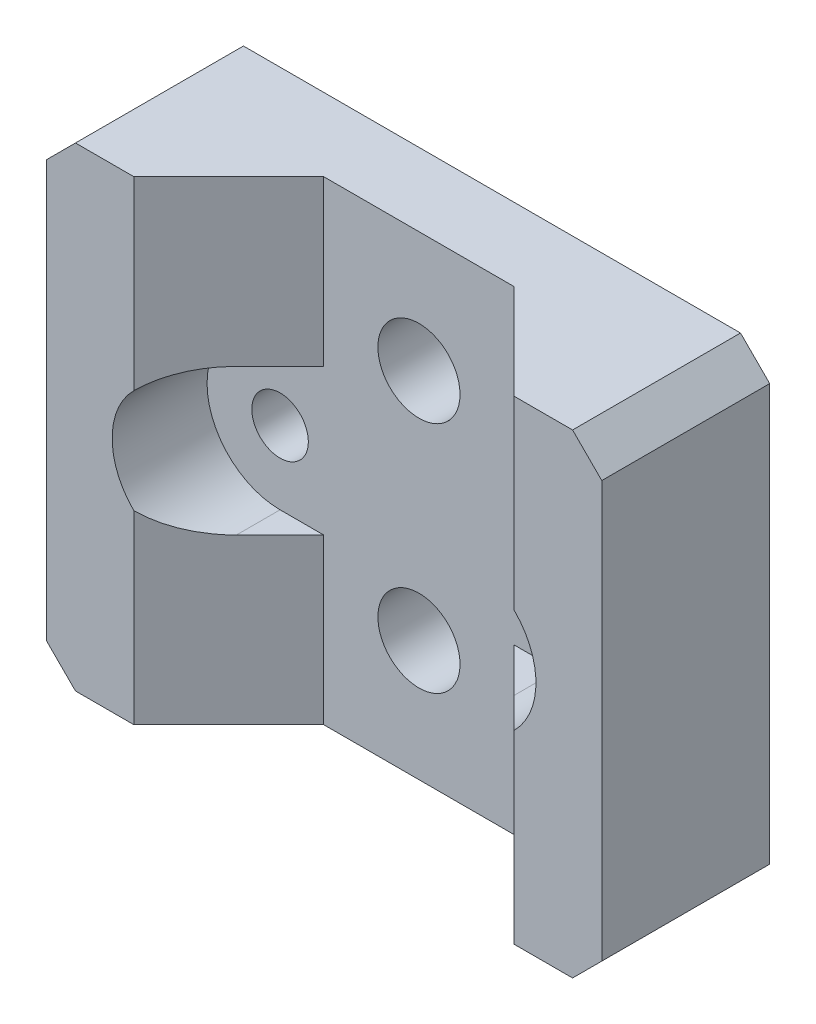
SolidWorks part; units mm, degrees
material "PET"
ref_plane "Front Plane" through (0, 0, 0) normal (0, 0, 1) x (1, 0, 0)
ref_plane "Top Plane" through (0, 0, 0) normal (0, 1, 0) x (1, 0, 0)
ref_plane "Right Plane" through (0, 0, 0) normal (1, 0, 0) x (0, 0, -1)
sketch "Sketch1" plane through (0, 0, 0) normal (0, 0, 1) x (1, 0, 0)
  line L0 (-124.0045, -34.7475) -> (-124.0045, -14.4275) construction
  line L1 (-148.1589, -8.5361) -> (-148.1589, -40.6389) construction
  line L2 (-148.1589, -3.95) -> (-99.85, -3.95)
  line L3 (-148.1589, -3.95) -> (-148.1589, -45.225)
  line L4 (-148.1589, -45.225) -> (-99.85, -45.225)
  line L5 (-99.85, -3.95) -> (-99.85, -45.225)
  line L6 (-148.1589, -3.95) -> (-99.85, -45.225) construction
  line L7 (-148.1589, -45.225) -> (-99.85, -3.95) construction
  point P4 (-124.0045, -24.5875)
  dimension "D1" = 41.275
extrude "Boss-Extrude1" add sketch "Sketch1" along normal blind 6.35
hole_wizard "#8 Clearance Hole1" positions "Sketch4" profile "Sketch5" hole size "#8" standard "ANSI Inch" end condition through all
sketch "Sketch4" plane through (0, 0, 6.35) normal (0, 0, 1) x (1, 0, 0)
  circle A0 centre (-111.9272, -24.5875) radius 2.9972 construction
  circle A1 centre (-136.0817, -24.5875) radius 2.9972 construction
  point P0 (-111.9272, -24.5875)
  point P2 (-136.0817, -24.5875)
sketch "Sketch5" plane through (-111.9272, -24.5875, 6.35) normal (1, 0, 0) x (0, -1, 0)
  line L0 (0, 0) -> (0, 6.35)
  line L1 (0, 6.35) -> (2.4574, 6.35)
  line L2 (2.4574, 6.35) -> (2.4574, 0)
  line L5 (2.4574, 0) -> (0, 0)
  line L11 (0, -6.35) -> (0, 107.95) construction
  dimension "Thru Hole Dia." = 4.9149
  dimension "Thru Hole Depth" = 6.35
hole_wizard "1/4 Clearance Hole1" positions "Sketch6" profile "Sketch7" hole size "1/4" standard "ANSI Inch" end condition through all
sketch "Sketch6" plane through (0, 0, 6.35) normal (0, 0, 1) x (1, 0, 0)
  circle A0 centre (-124.0045, -34.7475) radius 3.5712 construction
  circle A1 centre (-124.0045, -14.4275) radius 3.5712 construction
  point P0 (-124.0045, -14.4275)
  point P2 (-124.0045, -34.7475)
sketch "Sketch7" plane through (-124.0045, -14.4275, 6.35) normal (1, 0, 0) x (0, -1, 0)
  line L0 (0, 0) -> (0, 6.35)
  line L1 (0, 6.35) -> (3.5712, 6.35)
  line L2 (3.5712, 6.35) -> (3.5712, 0)
  line L5 (3.5712, 0) -> (0, 0)
  line L11 (0, -6.35) -> (0, 107.95) construction
  dimension "Thru Hole Dia." = 7.1425
  dimension "Thru Hole Depth" = 6.35
sketch "Sketch9" plane through (0, 0, 6.35) normal (0, 0, 1) x (1, 0, 0)
  line L4 (-99.85, -45.225) -> (-99.85, -3.95)
  line L5 (-99.85, -3.95) -> (-148.1589, -3.95)
  line L6 (-148.1589, -3.95) -> (-148.1589, -45.225)
  line L7 (-148.1589, -45.225) -> (-99.85, -45.225)
  line L8 (-99.85, -45.225) -> (-99.85, -3.95)
  line L10 (-148.1589, -3.95) -> (-148.1589, -45.225)
  dimension "D1" = 0
extrude "Extrude-Thin1" add sketch "Sketch9" along normal blind 8.255 thin thin type one direction reverse wall 6.35
chamfer "Chamfer2" distance 9.525 angle 45 2 edges at (-106.2, -24.5875, 6.35) (-141.8089, -24.5875, 6.35)
sketch "Sketch10" plane through (0, 0, 6.35) normal (0, 0, 1) x (1, 0, 0)
  line L0 (-136.0817, -24.5875) -> (-111.9272, -24.5875) construction
  line L1 (-136.0817, -18.2375) -> (-111.9272, -18.2375)
  line L2 (-136.0817, -30.9375) -> (-111.9272, -30.9375)
  arc A2 (-136.0817, -18.2375) -> (-136.0817, -30.9375) centre (-136.0817, -24.5875) ccw
  arc A3 (-111.9272, -30.9375) -> (-111.9272, -18.2375) centre (-111.9272, -24.5875) ccw
  point P3 (-124.0045, -24.5875)
  dimension "D1" = 6.35
extrude "Cut-Extrude1" cut sketch "Sketch10" along normal through all
chamfer "Chamfer1" distance 2.54 angle 45 4 edges at (-99.85, -3.95, 7.3025) (-148.1589, -3.95, 7.3025) (-99.85, -45.225, 7.3025) (-148.1589, -45.225, 7.3025)
hole_wizard "Hole1" positions "Sketch11" profile "Sketch12" legacy
sketch "Sketch11" plane through (-148.1589, 0, 0) normal (-1, 0, 0) x (0, 0, 1)
  point P0 (7.4422, -26.4544)
  point P3 (7.4422, -17.0945)
sketch "Sketch12" plane through (-148.1589, -26.4544, 7.4422) normal (0, 1, 0) x (0, 0, 1)
  line L0 (0, 0) -> (0, 2.921)
  line L1 (0, 2.921) -> (1.4986, 2.921)
  line L2 (1.4986, 2.921) -> (1.6383, 0)
  line L3 (1.6383, 0) -> (0, 0)
  line L4 (0, 110) -> (0, -10) construction
  dimension "Minor Diameter" = 2.9972
  dimension "Depth" = 2.921
  dimension "Major Diameter" = 3.2766
hole_wizard "#2 Clearance Hole1" positions "Sketch13" profile "Sketch14" hole size "#2" standard "ANSI Inch"
sketch "Sketch13" plane through (-148.1589, 0, 0) normal (-1, 0, 0) x (0, 0, 1)
  point P0 (7.4422, -17.0945)
  point P3 (7.4422, -26.4544)
sketch "Sketch14" plane through (-148.1589, -17.0945, 7.4422) normal (0, 1, 0) x (0, 0, 1)
  line L0 (0, 0) -> (0, 3.175)
  line L1 (0, 3.175) -> (1.3525, 3.175)
  line L2 (1.3525, 3.175) -> (1.3525, 0)
  line L5 (1.3525, 0) -> (0, 0)
  line L10 (0, 3.175) -> (-1.3526, 3.175) construction
  line L11 (0, -6.35) -> (0, 107.95) construction
  dimension "Hole Dia." = 2.7051
  dimension "Hole Depth" = 3.175
  dimension "Drill Angle" = 180
